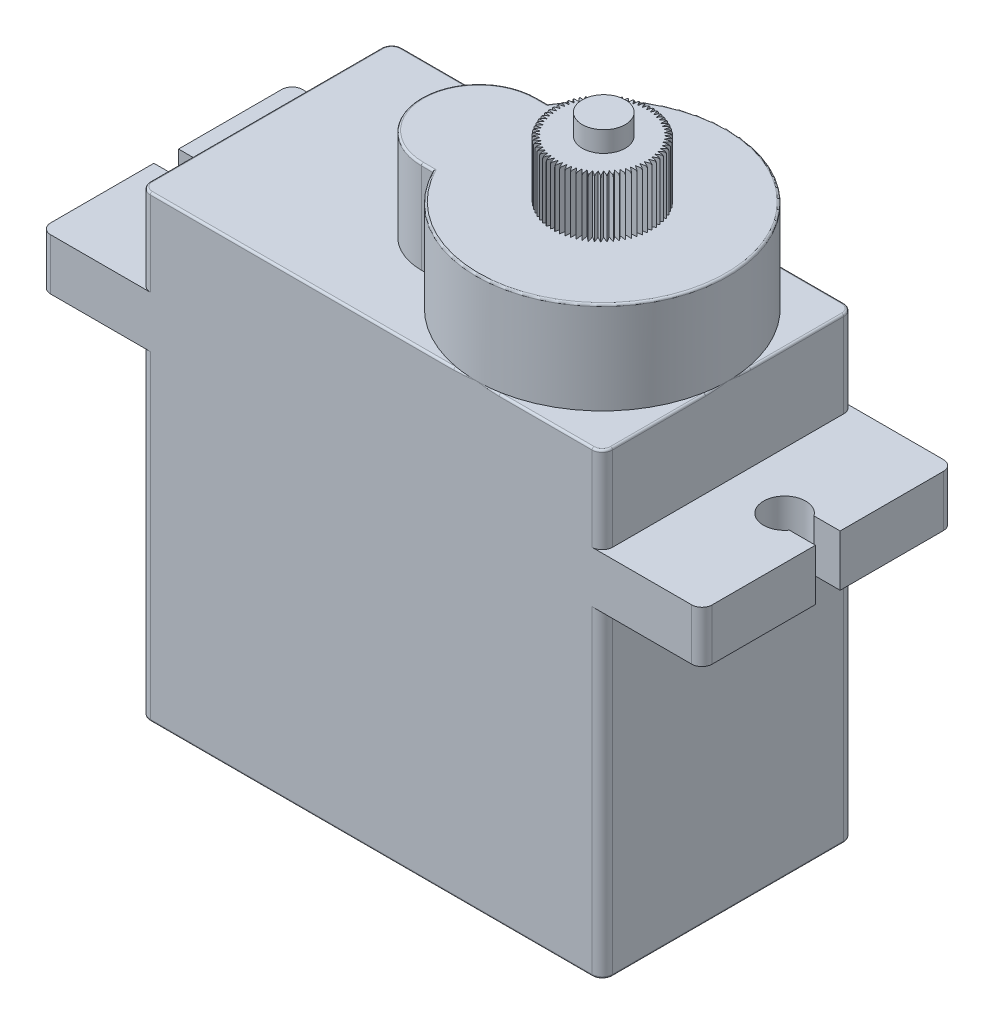
SolidWorks part; units mm, degrees
material "Q235"
ref_plane "前视" through (0, 0, 0) normal (0, 0, 1) x (1, 0, 0)
ref_plane "上视" through (0, 0, 0) normal (0, 1, 0) x (1, 0, 0)
ref_plane "右视" through (0, 0, 0) normal (1, 0, 0) x (0, 0, -1)
sketch "草图1" plane through (0, 0, 0) normal (0, 1, 0) x (1, 0, 0)
  line L1 (-11.25, 6.125) -> (11.25, 6.125)
  line L2 (-11.25, 6.125) -> (-11.25, -6.125)
  line L3 (-11.25, -6.125) -> (11.25, -6.125)
  line L4 (11.25, 6.125) -> (11.25, -6.125)
  line L5 (-11.25, 6.125) -> (11.25, -6.125) construction
  line L6 (-11.25, -6.125) -> (11.25, 6.125) construction
  point P0 (0, 0)
  dimension "D1" = 22.5
  dimension "D2" = 12.25
extrude "凸台-拉伸1" add sketch "草图1" along normal blind 15.6
sketch "草图2" plane through (0, 15.6, 0) normal (0, 1, 0) x (1, 0, 0)
  line L0 (0, 0) -> (20.5991, 0) construction
  line L1 (0, 0) -> (0, 10.7993) construction
  line L2 (11.25, 6.125) -> (16.1, 6.125)
  line L3 (16.1, 6.125) -> (16.1, 0.6)
  line L4 (11.25, -6.125) -> (11.25, 6.125)
  line L5 (11.25, 6.125) -> (-11.25, 6.125)
  line L6 (-11.25, 6.125) -> (-11.25, -6.125)
  line L7 (-11.25, -6.125) -> (11.25, -6.125)
  line L8 (-16.1, -0.6) -> (-14.831, -0.6)
  line L9 (11.25, 6.125) -> (-11.25, 6.125)
  line L10 (-16.1, 0.6) -> (-14.831, 0.6)
  line L11 (-11.25, -6.125) -> (11.25, -6.125)
  line L12 (16.1, -6.125) -> (11.25, -6.125)
  line L13 (16.1, 0.6) -> (14.831, 0.6)
  line L14 (16.1, -0.6) -> (14.831, -0.6)
  line L15 (16.1, -0.6) -> (16.1, -6.125)
  line L16 (-11.25, 6.125) -> (-16.1, 6.125)
  line L17 (-16.1, 6.125) -> (-16.1, 0.6)
  line L18 (-16.1, -6.125) -> (-11.25, -6.125)
  line L19 (-16.1, -0.6) -> (-16.1, -6.125)
  arc A0 (14.831, 0.6) -> (14.831, -0.6) centre (14, 0) ccw
  arc A1 (-14.831, 0.6) -> (-14.831, -0.6) centre (-14, 0) cw
  dimension "D3" = 2.05
  dimension "D2" = 4.85
  dimension "D4" = 14
  dimension "D5" = 1.2
  dimension "D6" = 1.269
  dimension "D1" = 0
extrude "凸台-拉伸2" add sketch "草图2" along normal blind 2.5
sketch "草图3" plane through (0, 18.1, 0) normal (0, 1, 0) x (1, 0, 0)
  line L4 (11.25, -6.125) -> (11.25, 6.125)
  line L5 (-11.25, -6.125) -> (11.25, -6.125)
  line L6 (-11.25, 6.125) -> (-11.25, -6.125)
  line L7 (11.25, 6.125) -> (-11.25, 6.125)
  line L8 (11.25, -6.125) -> (11.25, 6.125)
  line L9 (-11.25, -6.125) -> (11.25, -6.125)
  line L10 (-11.25, 6.125) -> (-11.25, -6.125)
  line L11 (11.25, 6.125) -> (-11.25, 6.125)
  dimension "D1" = 0
extrude "凸台-拉伸3" add sketch "草图3" along normal blind 4.2
sketch "草图4" plane through (0, 22.3, 0) normal (0, 1, 0) x (1, 0, 0)
  line L0 (11.25, -6.125) -> (11.25, 6.125) construction
  line L1 (-0.875, 2.8) -> (-0.3225, 2.8)
  line L2 (-0.875, -2.8) -> (-0.3225, -2.8)
  arc A0 (-0.3225, -2.8) -> (-0.3225, 2.8) centre (5.125, 0) ccw
  arc A1 (-0.875, 2.8) -> (-0.875, -2.8) centre (-0.875, 0) ccw
  dimension "D1" = 5.6
  dimension "D3" = 12.25
  dimension "D2" = 6
  dimension "D4" = 5.125
extrude "凸台-拉伸4" add sketch "草图4" along normal blind 4.5
sketch "草图5" plane through (0, 26.8, 0) normal (0, 1, 0) x (1, 0, 0)
  circle A0 centre (5.125, 0) radius 2.425
  dimension "D1" = 4.85
extrude "凸台-拉伸5" add sketch "草图5" along normal blind 2.8
fillet "圆角1" radius 0.5 12 edges at (11.25, 20.2, 6.125) (11.25, 20.2, -6.125) (16.1, 16.85, -6.125) (-16.1, 16.85, -6.125) (-11.25, 20.2, -6.125) (16.1, 16.85, 6.125) (-11.25, 20.2, 6.125) (-16.1, 16.85, 6.125) (-11.25, 7.8, -6.125) (11.25, 7.8, -6.125) (11.25, 7.8, 6.125) (-11.25, 7.8, 6.125)
fillet "圆角2" radius 0.1 24 edges at (11.1036, 0, -5.9786) (11.25, 0, 0) (11.1036, 0, 5.9786) (0, 0, 6.125) (-11.1036, 0, 5.9786) (-11.25, 0, 0) (-11.1036, 0, -5.9786) (7.9375, 22.3, -6.125) (11.1036, 22.3, -5.9786) (11.25, 22.3, -2.8125) (11.25, 22.3, 2.8125) (11.1036, 22.3, 5.9786) (7.9375, 22.3, 6.125) (-2.8125, 22.3, 6.125) (-11.1036, 22.3, 5.9786) (-11.25, 22.3, 0) (-11.1036, 22.3, -5.9786) (0, 0, -6.125) (-2.8125, 22.3, -6.125) (-0.5988, 26.8, -2.8) (-0.5988, 26.8, 2.8) (5.125, 29.6, 2.425) (-3.675, 26.8, 0) (11.25, 26.8, 0)
sketch "草图7" plane through (0, 29.6, 0) normal (0, 1, 0) x (1, 0, 0)
  line L0 (5.125, 0) -> (5.125, 1.3865) construction
  line L1 (4.975, 2.5351) -> (5.275, 2.5351)
  line L2 (5.275, 2.5351) -> (5.125, 2.1351)
  line L3 (5.125, 2.1351) -> (4.975, 2.5351)
  line L4 (5.125, 0) -> (4.1279, 0) construction
  dimension "D2" = 0.4
  dimension "D3" = 0.7485
  dimension "D1" = 0.3
extrude "切除-拉伸1" cut sketch "草图7" against normal up to surface (2.8 mm away)
pattern_circular "阵列(圆周)3" count 70 over 360 about axis through (5.125, 0, 0) along (0, 1, 0) of "切除-拉伸1"
sketch "草图8" plane through (0, 29.6, 0) normal (0, 1, 0) x (1, 0, 0)
  circle A0 centre (5.1961, 0) radius 1.0456
extrude "凸台-拉伸6" add sketch "草图8" along normal blind 1
